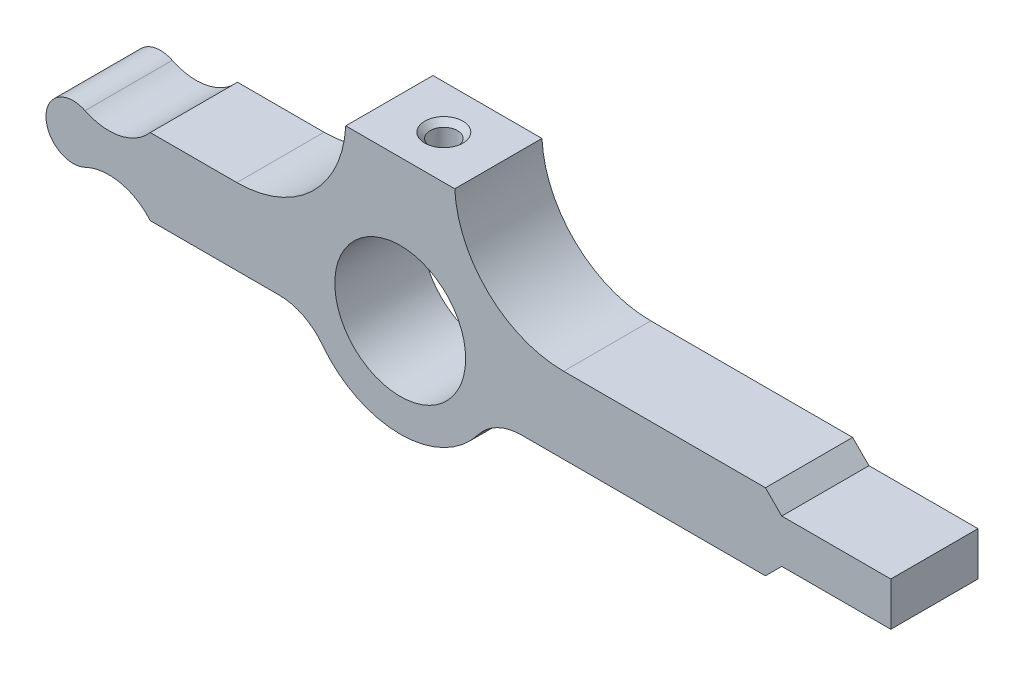
SolidWorks part; units mm, degrees
material "Латунь"
ref_plane "Спереди" through (0, 0, 0) normal (0, 0, 1) x (1, 0, 0)
ref_plane "Сверху" through (0, 0, 0) normal (0, 1, 0) x (1, 0, 0)
ref_plane "Справа" through (0, 0, 0) normal (1, 0, 0) x (0, 0, -1)
other "Таблица"
sketch "Эскиз1" plane through (0, 0, 0) normal (0, 0, 1) x (1, 0, 0)
  line L0 (0, -12.0069) -> (0, 16.897) construction
  line L1 (-35.289, 0) -> (48.5036, 0) construction
  line L2 (11.1243, -3.5) -> (33.5, -3.5)
  line L3 (33.5, -3.5) -> (35, -2)
  line L4 (35, -2) -> (45, -2)
  line L5 (45, -2) -> (45, 2)
  line L6 (45, 2) -> (35, 2)
  line L7 (35, 2) -> (33.5, 3.5)
  line L8 (33.5, 3.5) -> (14.9875, 3.5)
  line L9 (5, 13) -> (-5, 13)
  line L10 (-14.9875, 3.5) -> (-22.9312, 3.5)
  line L11 (-22.9312, -3.5) -> (-11.1243, -3.5)
  circle A0 centre (0, 0) radius 6
  arc A1 (-7.1513, -5.4643) -> (7.1513, -5.4643) centre (0, 0) ccw
  arc A2 (5, 13) -> (14.9875, 3.5) centre (14.9875, 13.5) ccw
  arc A3 (-5, 13) -> (-14.9875, 3.5) centre (-14.9875, 13.5) cw
  arc A4 (-22.9312, 3.5) -> (-28.9103, 2.25) centre (-26.7308, 6.75) cw
  arc A5 (-28.9103, 2.25) -> (-28.9103, -2.25) centre (-30, 0) ccw
  arc A6 (-28.9103, -2.25) -> (-22.9312, -3.5) centre (-26.7308, -6.75) cw
  arc A7 (7.1513, -5.4643) -> (11.1243, -3.5) centre (11.1243, -8.5) cw
  arc A8 (-11.1243, -3.5) -> (-7.1513, -5.4643) centre (-11.1243, -8.5) cw
  dimension "D21" = 12
  dimension "D4" = 10
  dimension "D5" = 3.5
  dimension "D13" = 5
  dimension "D14" = 9
  dimension "D16" = 5
  dimension "D12" = 2.5
  dimension "D18" = 22
  dimension "D22" = 10
  dimension "D6" = 7
  dimension "D8" = 4
  dimension "D10" = 10
  dimension "D11" = 45
  dimension "L1" = 32.5
  dimension "L2" = 45
extrude "Бобышка-Вытянуть1" add sketch "Эскиз1" along normal mid plane 8
hole_wizard "Отверстие обработанное метчиком M31" positions "Эскиз5" profile "Эскиз4" tap size "M3" standard "ISO" end condition up to next
sketch "Эскиз5" plane through (0, 13, 0) normal (0, 1, 0) x (1, 0, 0)
  point P0 (0, 0)
sketch "Эскиз4" plane through (0, 13, 0) normal (1, 0, 0) x (0, 0, 1)
  line L0 (0, 0) -> (0, 7)
  line L1 (0, 7) -> (1.25, 7)
  line L2 (1.25, 7) -> (1.25, 0.5)
  line L3 (1.25, 0.5) -> (1.75, 0)
  line L5 (1.75, 0) -> (0, 0)
  line L6 (-1.25, 0.5) -> (-1.75, 0) construction
  line L11 (0, -6.35) -> (0, 107.95) construction
  dimension "Диаметр проходного сверла" = 2.5
  dimension "Глубина проходного сверла" = 7
  dimension "Диаметр передней зенковки" = 3.5
  dimension "Угол передней зенковки" = 90
cosmetic thread "Отверстие резьбы1" parameters "D2"=3
